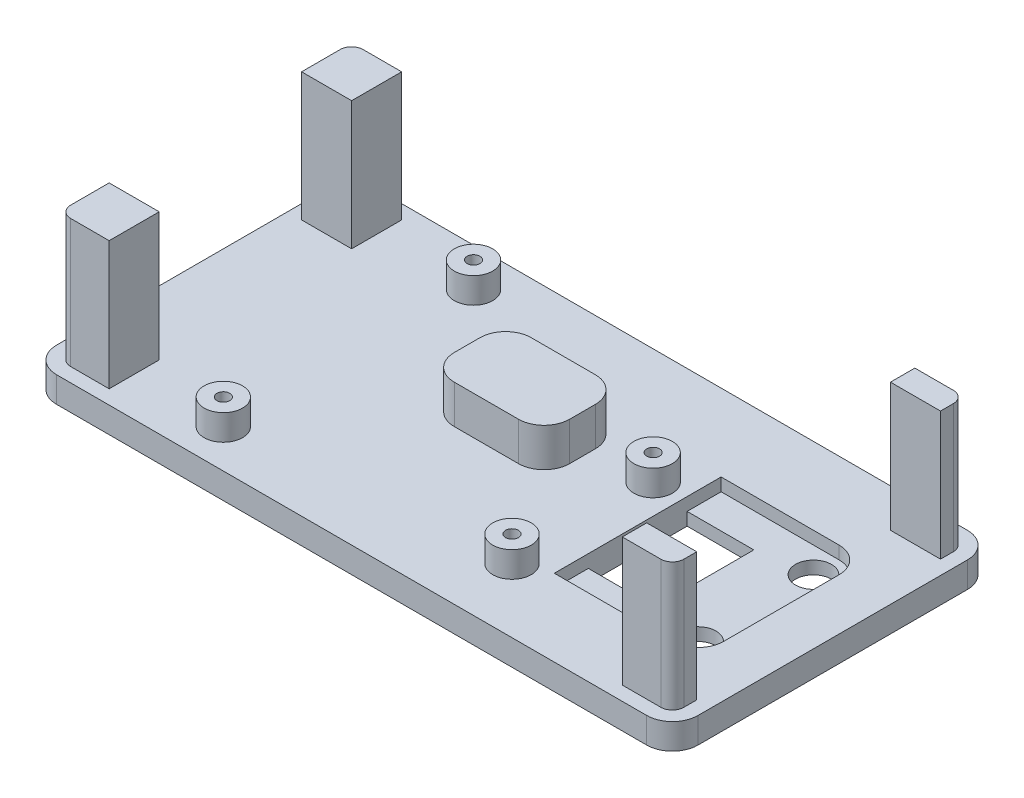
SolidWorks part; units mm, degrees
ref_plane "Front Plane" through (0, 0, 0) normal (0, 0, 1) x (1, 0, 0)
ref_plane "Top Plane" through (0, 0, 0) normal (0, 1, 0) x (1, 0, 0)
ref_plane "Right Plane" through (0, 0, 0) normal (1, 0, 0) x (0, 0, -1)
sketch "Sketch1" plane through (0, 0, 0) normal (0, 1, 0) x (1, 0, 0)
  line L1 (0, 0) -> (127, 0)
  line L2 (0, 0) -> (0, 63.5)
  line L3 (0, 63.5) -> (127, 63.5)
  line L4 (127, 0) -> (127, 63.5)
  dimension "D1" = 127
  dimension "D2" = 63.5
extrude "Boss-Extrude1" add sketch "Sketch1" along normal blind 5.08
sketch "Sketch2" plane through (0, 5.08, 0) normal (0, 1, 0) x (1, 0, 0)
  line L0 (63.5, 63.5) -> (63.5, 0) construction
  line L1 (127, 63.5) -> (0, 63.5) construction
  line L2 (0, 0) -> (127, 0) construction
  line L3 (0, 31.75) -> (127, 31.75) construction
  line L4 (0, 63.5) -> (0, 0) construction
  line L5 (127, 0) -> (127, 63.5) construction
  line L6 (12.7, 2.794) -> (12.7, 12.7)
  line L7 (2.794, 60.706) -> (12.7, 60.706)
  line L8 (2.794, 60.706) -> (2.794, 50.8)
  line L9 (2.794, 50.8) -> (12.7, 50.8)
  line L10 (12.7, 60.706) -> (12.7, 50.8)
  line L11 (2.794, 12.7) -> (12.7, 12.7)
  line L12 (2.794, 2.794) -> (2.794, 12.7)
  line L13 (2.794, 2.794) -> (12.7, 2.794)
  line L14 (124.206, 2.794) -> (124.206, 7.62)
  line L15 (114.3, 60.706) -> (124.206, 60.706)
  line L16 (114.3, 60.706) -> (114.3, 55.88)
  line L17 (114.3, 55.88) -> (124.206, 55.88)
  line L18 (124.206, 60.706) -> (124.206, 55.88)
  line L19 (114.3, 7.62) -> (124.206, 7.62)
  line L20 (114.3, 2.794) -> (114.3, 7.62)
  line L21 (114.3, 2.794) -> (124.206, 2.794)
  dimension "D1" = 9.906
  dimension "D2" = 9.906
  dimension "D3" = 2.794
  dimension "D4" = 2.794
  dimension "D5" = 2.794
  dimension "D6" = 2.794
  dimension "D7" = 4.826
  dimension "D8" = 9.906
extrude "Boss-Extrude3" add sketch "Sketch2" along normal blind 25.4
fillet "Fillet3" radius 2.286 4 edges at (124.206, 17.78, -60.706) (124.206, 17.78, -2.794) (2.794, 17.78, -2.794) (2.794, 17.78, -60.706)
fillet "Fillet4" radius 5.08 4 edges at (0, 2.54, -63.5) (127, 2.54, -63.5) (127, 2.54, 0) (0, 2.54, 0)
sketch "Sketch4" plane through (0, 5.08, 0) normal (0, 1, 0) x (1, 0, 0)
  circle A0 centre (31.75, 55.88) radius 3.81
  circle A1 centre (30.48, 7.62) radius 3.81
  circle A2 centre (82.55, 40.64) radius 3.81
  circle A3 centre (82.55, 12.7) radius 3.81
  circle A4 centre (31.75, 55.88) radius 1.27
  circle A5 centre (82.55, 40.64) radius 1.27
  circle A6 centre (30.48, 7.62) radius 1.27
  circle A7 centre (82.55, 12.7) radius 1.27
  dimension "D1" = 7.62
  dimension "D2" = 7.62
  dimension "D7" = 50.8
  dimension "D11" = 7.62
  dimension "D12" = 7.62
  dimension "D13" = 2.54
  dimension "D8" = 2.54
  dimension "D14" = 2.54
  dimension "D15" = 2.54
  dimension "D3" = 15.24
  dimension "D4" = 19.05
  dimension "D5" = 48.26
  dimension "D6" = 7.62
  dimension "D9" = 27.94
  dimension "D10" = 52.07
sketch "Sketch7" plane through (0, 5.08, 0) normal (0, 1, 0) x (1, 0, 0)
  line L0 (121.92, 63.5) -> (5.08, 63.5) construction
  line L1 (48.26, 45.72) -> (71.12, 45.72)
  line L2 (48.26, 45.72) -> (48.26, 30.48)
  line L3 (48.26, 30.48) -> (71.12, 30.48)
  line L4 (71.12, 45.72) -> (71.12, 30.48)
  dimension "D1" = 22.86
  dimension "D2" = 17.78
  dimension "D3" = 30.48
  dimension "D4" = 43.18
sketch "Sketch13" plane through (0, 5.08, 0) normal (0, 1, 0) x (1, 0, 0)
  line L0 (121.92, 63.5) -> (5.08, 63.5) construction
  line L1 (5.08, 0) -> (121.92, 0) construction
  line L2 (127, 5.08) -> (127, 58.42) construction
  line L4 (88.392, 41.529) -> (101.6, 41.529)
  line L5 (88.392, 41.529) -> (88.392, 21.971)
  line L6 (88.392, 21.971) -> (101.6, 21.971)
  line L7 (101.6, 41.529) -> (101.6, 21.971)
  circle A0 centre (111.76, 43.18) radius 3.556
  circle A1 centre (111.76, 20.32) radius 3.556
  dimension "D1" = 7.112
  dimension "D2" = 7.112
  dimension "D3" = 20.32
  dimension "D4" = 20.32
  dimension "D5" = 15.24
  dimension "D6" = 19.558
  dimension "D7" = 13.208
  dimension "D8" = 25.4
  dimension "D9" = 16.891
extrude "Cut-Extrude8" cut sketch "Sketch13" against normal up to next
sketch "Sketch14" plane through (0, 5.08, 0) normal (0, 1, 0) x (1, 0, 0)
  line L0 (88.392, 41.529) -> (88.392, 21.971) construction
  line L1 (88.392, 46.609) -> (101.6, 46.609)
  line L2 (88.392, 46.609) -> (88.392, 16.891)
  line L3 (88.392, 16.891) -> (101.6, 16.891)
  line L4 (101.6, 46.609) -> (101.6, 16.891)
  line L5 (101.6, 21.971) -> (101.6, 41.529) construction
  dimension "D1" = 5.08
  dimension "D2" = 5.08
extrude "Cut-Extrude9" cut sketch "Sketch14" against normal blind 2.54
sketch "Sketch19" plane through (0, 5.08, 0) normal (0, 1, 0) x (1, 0, 0)
  circle A0 centre (111.76, 43.18) radius 5.08
  circle A1 centre (111.76, 20.32) radius 5.08
  dimension "D1" = 10.16
  dimension "D2" = 10.16
extrude "Cut-Extrude12" cut sketch "Sketch19" against normal blind 2.54
extrude "Boss-Extrude13" add sketch "Sketch4" along normal blind 5.08
extrude "Boss-Extrude14" add sketch "Sketch7" along normal blind 7.62
fillet "Fillet5" radius 5.08 4 edges at (48.26, 8.89, -45.72) (71.12, 8.89, -45.72) (71.12, 8.89, -30.48) (48.26, 8.89, -30.48)
sketch "Sketch21" plane through (0, 5.08, 0) normal (0, 1, 0) x (1, 0, 0)
  line L0 (111.76, 48.26) -> (88.392, 48.26)
  line L1 (88.392, 15.24) -> (88.392, 48.26)
  line L2 (111.76, 15.24) -> (88.392, 15.24)
  line L4 (116.84, 20.32) -> (116.84, 43.18)
  circle A0 centre (111.76, 43.18) radius 5.08 construction
  circle A1 centre (111.76, 43.18) radius 5.08 construction
  circle A2 centre (111.76, 20.32) radius 5.08 construction
  circle A3 centre (111.76, 20.32) radius 5.08 construction
  arc A4 (111.76, 48.26) -> (116.84, 43.18) centre (111.76, 43.18) cw
  arc A5 (111.76, 15.24) -> (116.84, 20.32) centre (111.76, 20.32) ccw
  dimension "D1" = 33.02
  dimension "D2" = 23.368
extrude "Cut-Extrude13" cut sketch "Sketch21" against normal blind 2.54
